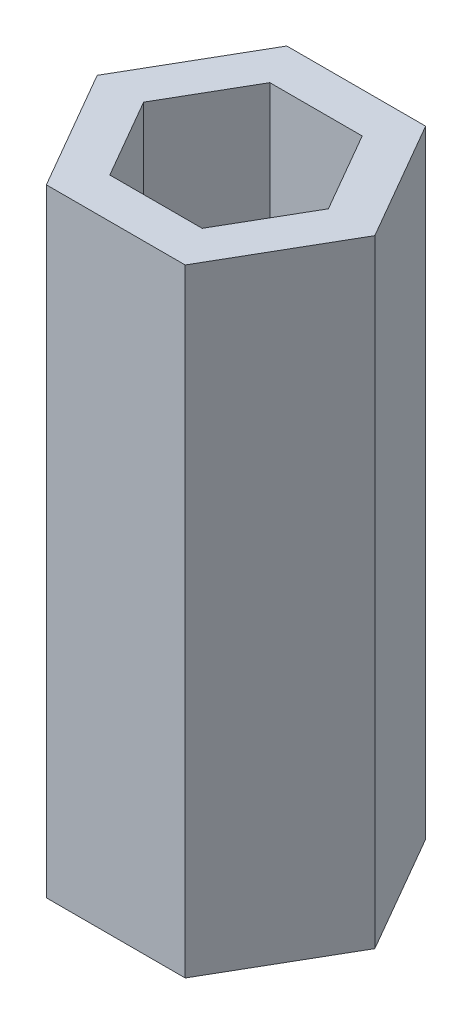
SolidWorks part; units mm, degrees
ref_plane "Front Plane" through (0, 0, 0) normal (0, 0, 1) x (1, 0, 0)
ref_plane "Top Plane" through (0, 0, 0) normal (0, 1, 0) x (1, 0, 0)
ref_plane "Right Plane" through (0, 0, 0) normal (1, 0, 0) x (0, 0, -1)
sketch "Sketch1" plane through (0, 0, 0) normal (0, 1, 0) x (1, 0, 0)
  line L1 (4.0988, 0) -> (2.0494, 3.5496)
  line L2 (2.0494, 3.5496) -> (-2.0494, 3.5496)
  line L3 (-2.0494, 3.5496) -> (-4.0988, 0)
  line L4 (-4.0988, 0) -> (-2.0494, -3.5497)
  line L5 (-2.0494, -3.5497) -> (2.0494, -3.5496)
  line L6 (2.0494, -3.5496) -> (4.0988, 0)
  line L7 (6.1592, 0) -> (3.0796, 5.334)
  line L8 (3.0796, 5.334) -> (-3.0796, 5.334)
  line L9 (-3.0796, 5.334) -> (-6.1592, 0)
  line L10 (-6.1592, 0) -> (-3.0796, -5.334)
  line L11 (-3.0796, -5.334) -> (3.0796, -5.334)
  line L12 (3.0796, -5.334) -> (6.1592, 0)
  circle A0 centre (0, 0) radius 3.5497 construction
  circle A1 centre (0, 0) radius 5.334 construction
  dimension "D1" = 7.0993
  dimension "D2" = 10.668
extrude "Boss-Extrude1" add sketch "Sketch1" along normal blind 27.3977
